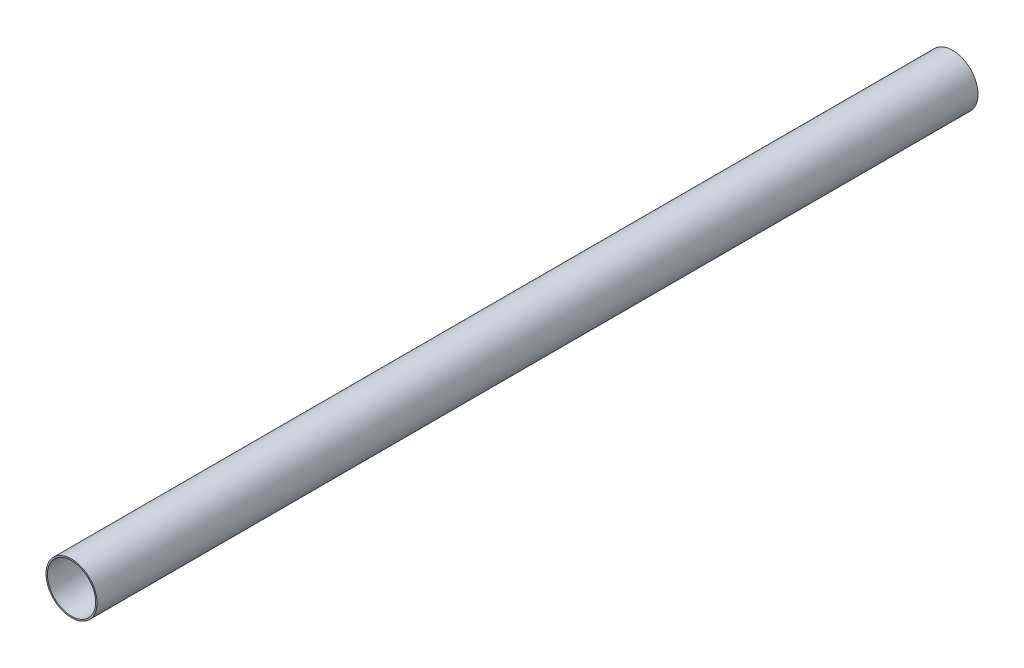
SolidWorks part; units mm, degrees
ref_plane "Ebene vorne" through (0, 0, 0) normal (0, 0, 1) x (1, 0, 0)
ref_plane "Ebene oben" through (0, 0, 0) normal (0, 1, 0) x (1, 0, 0)
ref_plane "Ebene rechts" through (0, 0, 0) normal (1, 0, 0) x (0, 0, -1)
sketch "Skizze1" plane through (0, 0, 0) normal (0, 0, 1) x (1, 0, 0)
  circle A3 centre (0, 0) radius 55
  dimension "D1" = 110
extrude "Aufsatz-Linear austragen2" add sketch "Skizze1" along normal blind 1900 contours A3
shell "Wandung2" thickness 3 removed face at (55, 0, 0) removed face at (55, 0, 1900)
ref_axis "Achse1" through (0, 0, 2670.4866) along (0, 0, -1)
